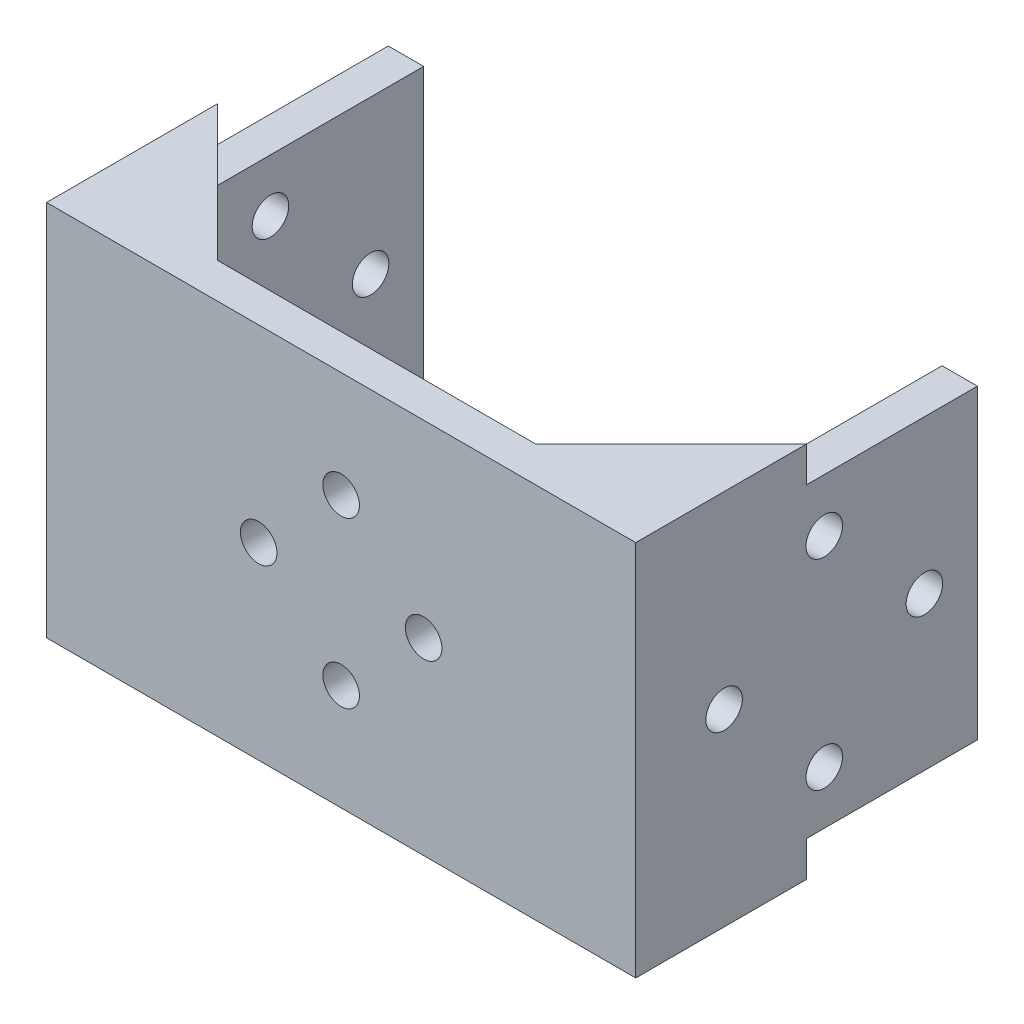
SolidWorks part; units mm, degrees
ref_plane "Front Plane" through (0, 0, 0) normal (0, 0, 1) x (1, 0, 0)
ref_plane "Top Plane" through (0, 0, 0) normal (0, 1, 0) x (1, 0, 0)
ref_plane "Right Plane" through (0, 0, 0) normal (1, 0, 0) x (0, 0, -1)
sketch "Sketch1" plane through (0, 0, 0) normal (0, 0, 1) x (1, 0, 0)
  line L0 (-7, 0) -> (7, 0) construction
  line L2 (-25, -13) -> (25, -13)
  line L3 (-25, -13) -> (-25, 13)
  line L4 (-25, 13) -> (25, 13)
  line L5 (25, -13) -> (25, 13)
  line L6 (-25, -13) -> (25, 13) construction
  line L7 (-25, 13) -> (25, -13) construction
  circle A0 centre (-7, 0) radius 1.55
  circle A2 centre (0, 7) radius 1.55
  circle A3 centre (7, 0) radius 1.55
  circle A4 centre (0, -7) radius 1.55
  point P4 (0, 0)
  point P6 (0, 0)
  point P15 (0, 0)
  dimension "D1" = 4
extrude "Boss-Extrude1" add sketch "Sketch1" along normal blind 3
sketch "Sketch2" plane through (-25, 0, 0) normal (-1, 0, 0) x (0, 0, 1)
  line L0 (3, -13) -> (3, 13)
  line L1 (3, -13) -> (-26, -13)
  line L2 (3, 13) -> (-26, 13)
  line L3 (-26, -13) -> (-26, 13)
  line L4 (0, 13) -> (0, -13) construction
  line L5 (-13, 0) -> (-4.5, 0) construction
  line L6 (0, 0) -> (-13, 0) construction
  circle A0 centre (-4.5, 0) radius 1.55
  circle A1 centre (-13, -8.5) radius 1.55
  circle A2 centre (-21.5, 0) radius 1.55
  circle A3 centre (-13, 8.5) radius 1.55
  point P23 (-13, 0)
  dimension "D1" = 4
extrude "Boss-Extrude2" add sketch "Sketch2" against normal blind 3
extrude "Boss-Extrude3" add sketch "Sketch2<2>" along normal blind 3 from surface starting at face at (25, 0, 1.5)
sketch "Sketch2<2>" plane through (-25, 0, 0) normal (-1, 0, 0) x (0, 0, 1) same geometry as "Sketch2"
sketch "Sketch3" plane through (0, 13, 0) normal (0, 1, 0) x (1, 0, 0)
  line L0 (-25, -3) -> (-25, 11.5)
  line L1 (-25, -3) -> (-25, 26) construction
  line L5 (25, -3) -> (25, 11.5)
  line L6 (25, -3) -> (25, 26) construction
  line L9 (25, 11.5) -> (13.5, 0)
  line L10 (22, 0) -> (-22, 0) construction
  line L11 (-25, 11.5) -> (-13.5, 0)
  line L12 (-13.5, 0) -> (13.5, 0)
  line L13 (-25, -3) -> (25, -3)
extrude "Boss-Extrude4" add sketch "Sketch3" along normal blind 3
extrude "Boss-Extrude5" add sketch "Sketch3<3>" against normal blind 3 from surface starting at face at (0, -13, -12.25)
sketch "Sketch3<3>" plane through (0, 13, 0) normal (0, 1, 0) x (1, 0, 0) same geometry as "Sketch3"
